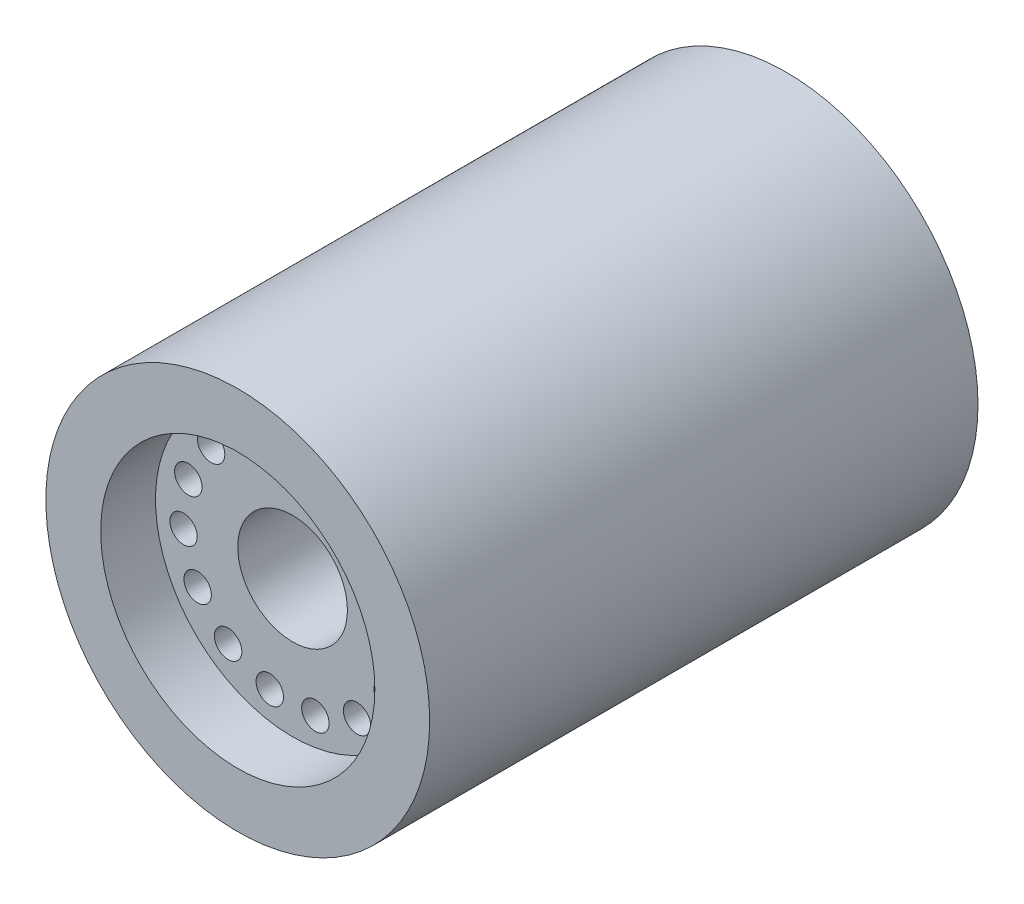
SolidWorks part; units mm, degrees
ref_plane "Front Plane" through (0, 0, 0) normal (0, 0, 1) x (1, 0, 0)
ref_plane "Top Plane" through (0, 0, 0) normal (0, 1, 0) x (1, 0, 0)
ref_plane "Right Plane" through (0, 0, 0) normal (1, 0, 0) x (0, 0, -1)
sketch "Sketch1" plane through (0, 0, 0) normal (0, 0, 1) x (1, 0, 0)
  circle A0 centre (0, 0) radius 35
  dimension "D1" = 70
extrude "Boss-Extrude1" add sketch "Sketch1" along normal blind 100
sketch "Sketch2" plane through (0, 0, 100) normal (0, 0, 1) x (1, 0, 0)
  circle A0 centre (0, 0) radius 25
  circle A1 centre (0, 0) radius 2.5
  circle A2 centre (0, 20) radius 2.5
  circle A3 centre (0, 0) radius 25
  circle A4 centre (8.1347, 18.2709) radius 2.5
  circle A5 centre (0, 0) radius 25
  circle A6 centre (14.8629, 13.3826) radius 2.5
  circle A7 centre (0, 0) radius 25
  circle A8 centre (19.0211, 6.1803) radius 2.5
  circle A9 centre (0, 0) radius 25
  circle A10 centre (19.8904, -2.0906) radius 2.5
  circle A11 centre (0, 0) radius 25
  circle A12 centre (17.3205, -10) radius 2.5
  circle A13 centre (0, 0) radius 25
  circle A14 centre (11.7557, -16.1803) radius 2.5
  circle A15 centre (0, 0) radius 25
  circle A16 centre (4.1582, -19.563) radius 2.5
  circle A17 centre (0, 0) radius 25
  circle A18 centre (-4.1582, -19.563) radius 2.5
  circle A19 centre (0, 0) radius 25
  circle A20 centre (-11.7557, -16.1803) radius 2.5
  circle A21 centre (0, 0) radius 25
  circle A22 centre (-17.3205, -10) radius 2.5
  circle A23 centre (0, 0) radius 25
  circle A24 centre (-19.8904, -2.0906) radius 2.5
  circle A25 centre (0, 0) radius 25
  circle A26 centre (-19.0211, 6.1803) radius 2.5
  circle A27 centre (0, 0) radius 25
  circle A28 centre (-14.8629, 13.3826) radius 2.5
  circle A29 centre (0, 0) radius 25
  circle A30 centre (-8.1347, 18.2709) radius 2.5
  point P51 (0, 0)
  dimension "D1" = 50
  dimension "D2" = 5
  dimension "D3" = 5
  dimension "D4" = 20
  dimension "D5" = 15
extrude "Cut-Extrude5" cut sketch "Sketch2" against normal blind 15 contours A2 | A30 | A28 | A26 | A22 | A20 | A24 | A18 | A16 | A10 | A14 | A8 | A12 | A6 | A4
extrude "Cut-Extrude6" cut sketch "Sketch2<7>" against normal blind 10 contours A0
sketch "Sketch2<7>" plane through (0, 0, 100) normal (0, 0, 1) x (1, 0, 0) same geometry as "Sketch2"
sketch "Sketch3" plane through (0, 0, 0) normal (0, 0, 1) x (1, 0, 0)
  circle A0 centre (0, 0) radius 10
  dimension "D1" = 20
extrude "Cut-Extrude8" cut sketch "Sketch3" along normal through all
hole_wizard "1/4-20 Tapped Hole1" positions "3DSketch1" profile "Sketch5" tap size "1/4-20" standard "ANSI Inch"
sketch3d "3DSketch1"
  point P0 (0.9513, -34.9871, 51.6959)
sketch "Sketch5" plane through (0.9513, -34.9871, 51.6959) normal (0, 0, 1) x (0.9996, 0.0272, 0)
  line L0 (0, 0) -> (0, 20.6338)
  line L1 (0, 20.6338) -> (2.5527, 19.1)
  line L2 (2.5527, 19.1) -> (2.5527, 0)
  line L5 (2.5527, 0) -> (0, 0)
  line L10 (0, 20.6338) -> (-2.5527, 19.1) construction
  line L11 (0, -6.35) -> (0, 107.95) construction
  dimension "Tap Drill Dia." = 5.1054
  dimension "Tap Drill Depth" = 19.1
  dimension "Drill Angle" = 118
cosmetic thread "Hole Thread1" parameters "D1"=12.7, "D2"=6.35
